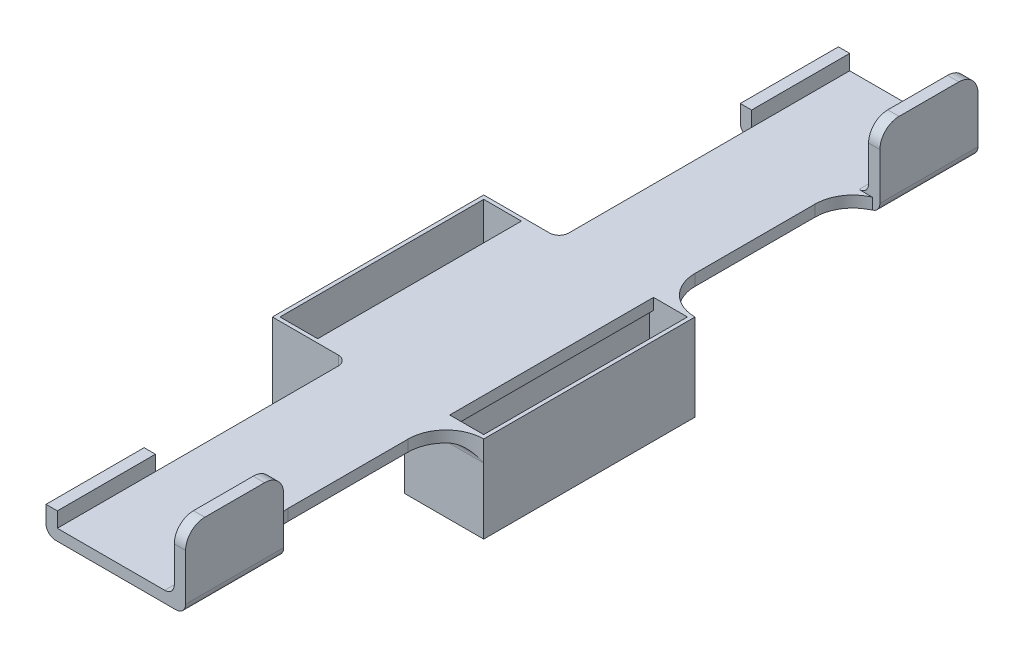
SolidWorks part; units mm, degrees
ref_plane "Front Plane" through (0, 0, 0) normal (0, 0, 1) x (1, 0, 0)
ref_plane "Top Plane" through (0, 0, 0) normal (0, 1, 0) x (1, 0, 0)
ref_plane "Right Plane" through (0, 0, 0) normal (1, 0, 0) x (0, 0, -1)
sketch "Sketch1" plane through (0, 0, 0) normal (0, 1, 0) x (1, 0, 0)
  line L1 (14, -14) -> (-14, -14)
  line L2 (14, -14) -> (14, 14)
  line L3 (14, 14) -> (-14, 14)
  line L4 (-14, -14) -> (-14, 14)
  line L5 (14, -14) -> (-14, 14) construction
  line L6 (14, 14) -> (-14, -14) construction
  line L7 (13.5, 13.5) -> (-13.5, 13.5)
  line L8 (13.5, 13.5) -> (13.5, -13.5)
  line L9 (13.5, -13.5) -> (-13.5, -13.5)
  line L10 (-13.5, 13.5) -> (-13.5, -13.5)
  line L11 (13.5, 13.5) -> (-13.5, -13.5) construction
  line L12 (13.5, -13.5) -> (-13.5, 13.5) construction
  point P0 (0, 0)
  point P6 (0, 0)
  dimension "D1" = 28
  dimension "D2" = 28
  dimension "D3" = 27
  dimension "D4" = 27
extrude "Boss-Extrude1" add sketch "Sketch1" along normal blind 5
sketch "Sketch2" plane through (0, 5, 0) normal (0, 1, 0) x (1, 0, 0)
  line L0 (-13.5, 13.5) -> (-13.5, -13.5) construction
  line L1 (-13.5, 13.5) -> (-13.5, -13.5)
  line L2 (-13.5, -13.5) -> (13.5, -13.5) construction
  line L3 (13.5, -13.5) -> (13.5, 13.5) construction
  line L4 (13.5, 13.5) -> (-13.5, 13.5) construction
  line L5 (-13.5, -13.5) -> (13.5, -13.5)
  line L6 (13.5, -13.5) -> (13.5, 13.5)
  line L7 (13.5, 13.5) -> (-13.5, 13.5)
extrude "Boss-Extrude2" add sketch "Sketch2" against normal blind 1 separate body
sketch "Sketch4" plane through (0, 0, 0) normal (0, -1, 0) x (1, 0, 0)
  line L0 (-14, 14) -> (14, 14) construction
  line L1 (-3.5, 14) -> (3.5, 14)
  line L2 (-3.5, 14) -> (-3.5, 13.5)
  line L3 (-3.5, 13.5) -> (3.5, 13.5)
  line L4 (3.5, 14) -> (3.5, 13.5)
  line L5 (-13.5, 13.5) -> (13.5, 13.5) construction
  line L6 (0, 0) -> (13.5, 0) construction
  line L7 (13.5, 13.5) -> (13.5, -13.5) construction
  line L8 (-3.5, -13.5) -> (3.5, -13.5)
  line L9 (3.5, -14) -> (3.5, -13.5)
  line L10 (-3.5, -14) -> (3.5, -14)
  line L11 (-3.5, -14) -> (-3.5, -13.5)
  dimension "D1" = 3.5
  dimension "D2" = 3.5
extrude "Cut-Extrude1" cut sketch "Sketch4" against normal up to surface (4 mm away) up to face at (0, 4, 0)
sketch "Sketch5" plane through (0, 4, 0) normal (0, -1, 0) x (1, 0, 0)
  line L0 (13.5, -13.5) -> (-13.5, -13.5) construction
  line L1 (-13.5, 13.5) -> (-8.5, 13.5)
  line L2 (-13.5, 13.5) -> (-13.5, -13.5)
  line L3 (-13.5, -13.5) -> (-8.5, -13.5)
  line L4 (-8.5, 13.5) -> (-8.5, -13.5)
  line L5 (0, 0) -> (0, 13.5) construction
  line L6 (-3.5, 13.5) -> (3.5, 13.5) construction
  line L7 (13.5, -13.5) -> (8.5, -13.5)
  line L8 (8.5, 13.5) -> (8.5, -13.5)
  line L9 (13.5, 13.5) -> (8.5, 13.5)
  line L10 (13.5, 13.5) -> (13.5, -13.5)
  dimension "D1" = 5
extrude "Cut-Extrude2" cut sketch "Sketch5" against normal through all both and the other way through all
sketch "Sketch6" plane through (0, 4, 0) normal (0, -1, 0) x (1, 0, 0)
  line L0 (-8.5, -1.5) -> (0, -1.5) construction
  line L2 (-8.5, -10.5) -> (0, -10.5) construction
  line L3 (0, 13.5) -> (0, -13.5) construction
  line L4 (-3.5, 13.5) -> (3.5, 13.5) construction
  line L5 (3.5, -13.5) -> (-3.5, -13.5) construction
  line L6 (8.5, -13.5) -> (-8.5, -13.5) construction
  line L8 (0, 0) -> (-8.5, 0) construction
  line L9 (-8.5, 13.5) -> (-8.5, -13.5) construction
  line L24 (-1.5, 0) -> (-1.5, -13.5) construction
  line L25 (-7, -13.5) -> (-7, 0) construction
  line L26 (-7, -10.5) -> (-1.5, -1.5)
  line L27 (-1.5, -1.5) -> (-1.5, -10.5)
  line L28 (-1.5, -10.5) -> (-7, -10.5)
  line L29 (-1.5, 10.5) -> (-7, 10.5)
  line L30 (-7, 10.5) -> (-1.5, 1.5)
  line L31 (-1.5, 1.5) -> (-1.5, 10.5)
  line L32 (1.5, 1.5) -> (1.5, 10.5)
  line L33 (1.5, 10.5) -> (7, 10.5)
  line L34 (7, 10.5) -> (1.5, 1.5)
  line L35 (7, -10.5) -> (1.5, -1.5)
  line L36 (1.5, -10.5) -> (7, -10.5)
  line L37 (1.5, -1.5) -> (1.5, -10.5)
  line L38 (-7, -9) -> (-1.5, 0)
  line L39 (-7, 9) -> (-1.5, 0)
  line L40 (7, 9) -> (1.5, 0)
  line L41 (7, -9) -> (1.5, 0)
  line L42 (-7, 9) -> (-7, -9)
  line L43 (7, 9) -> (7, -9)
  point P15 (-1.5, -10.5)
  point P19 (-7, -10.5)
  point P21 (-1.5, -1.5)
  point P23 (-7, -1.5)
  point P37 (-7, -9)
  dimension "D1" = 1.5
  dimension "D2" = 3
  dimension "D3" = 1.5
  dimension "D4" = 1.5
  dimension "D5" = 1.5
sketch "Sketch7" plane through (0, 4, 0) normal (0, -1, 0) x (1, 0, 0)
  line L0 (8.5, -13.5) -> (-8.5, -13.5) construction
  line L1 (-8.5, 13.5) -> (-3.5, 13.5)
  line L2 (-8.5, 13.5) -> (-8.5, -13.5)
  line L3 (-8.5, -13.5) -> (-3.5, -13.5)
  line L4 (-3.5, 13.5) -> (-3.5, -13.5)
  line L5 (-3.5, -13.5) -> (-13.5, -13.5) construction
  line L6 (13.5, -13.5) -> (3.5, -13.5) construction
  line L7 (8.5, 13.5) -> (3.5, 13.5)
  line L8 (8.5, 13.5) -> (8.5, -13.5)
  line L9 (8.5, -13.5) -> (3.5, -13.5)
  line L10 (3.5, 13.5) -> (3.5, -13.5)
extrude "Boss-Extrude3" add sketch "Sketch7" against normal up to surface (1 mm away) and the other way up to surface (4 mm away) up to face at (0, 5, 0) other way up to face at (8.625, 0, 0)
sketch "Sketch8" plane through (0, 0, 0) normal (0, -1, 0) x (1, 0, 0)
  line L0 (-13.5, -13.5) -> (-13.5, 13.5) construction
  line L5 (-3.5, -14) -> (-14, -14) construction
  line L6 (-14, -14) -> (-14, 14) construction
  line L7 (-14, 14) -> (-3.5, 14) construction
  line L8 (-13.5, -13.5) -> (-13.5, 13.5)
  line L13 (-3.5, -14) -> (-14, -14)
  line L14 (-14, -14) -> (-14, 14)
  line L15 (-14, 14) -> (-3.5, 14)
  line L17 (-13.5, -13.5) -> (-3.5, -13.5)
  line L18 (-3.5, 14) -> (-3.5, -14) construction
  line L23 (-3.5, 14) -> (-3.5, -14) construction
  line L29 (-3.5, 14) -> (-3.5, 13.5)
  line L30 (-3.5, -13.5) -> (-3.5, -14)
  line L31 (-13.5, 13.5) -> (-3.5, 13.5)
  line L32 (-3.5, 14) -> (-3.5, -14) construction
  line L35 (0, 14) -> (0, 0) construction
  line L36 (3.5, 14) -> (-3.5, 14) construction
  line L37 (3.5, -13.5) -> (3.5, -14)
  line L38 (13.5, -13.5) -> (3.5, -13.5)
  line L39 (3.5, -14) -> (14, -14)
  line L40 (14, -14) -> (14, 14)
  line L41 (13.5, -13.5) -> (13.5, 13.5)
  line L42 (3.5, 14) -> (3.5, 13.5)
  line L43 (14, 14) -> (3.5, 14)
  line L44 (13.5, 13.5) -> (3.5, 13.5)
extrude "Boss-Extrude4" add sketch "Sketch8" along normal blind 5 contours L17 L30 L13 L14 L15 L29 L31 L8
sketch "Sketch9" plane through (0, 0, 0) normal (0, -1, 0) x (1, 0, 0)
  line L6 (3.5, 14) -> (14, 14)
  line L10 (14, 14) -> (14, -14)
  line L11 (14, -14) -> (3.5, -14)
  line L12 (3.5, -14) -> (3.5, -13.5)
  line L13 (13.5, 13.5) -> (3.5, 13.5)
  line L14 (13.5, -13.5) -> (3.5, -13.5)
  line L15 (13.5, -13.5) -> (13.5, 13.5)
  line L16 (3.5, 13.5) -> (3.5, 14)
extrude "Boss-Extrude5" add sketch "Sketch9" along normal blind 5
sketch "Sketch10" plane through (0, 5, 0) normal (0, 1, 0) x (1, 0, 0)
  line L0 (9, 14.6081) -> (9, -15.0682) construction
  line L1 (14, -14) -> (14, 14) construction
  line L2 (-4, 14.6081) -> (-4, -15.0682) construction
  line L3 (0, 0) -> (9, 0) construction
  line L4 (-4, 52.5) -> (9, 52.5)
  line L5 (-4, 52.5) -> (-4, -52.5)
  line L6 (-4, -52.5) -> (9, -52.5)
  line L7 (9, 52.5) -> (9, -52.5)
  dimension "D1" = 5
  dimension "D2" = 13
  dimension "D3" = 52.5
  dimension "D4" = 52.5
extrude "Boss-Extrude6" add sketch "Sketch10" along normal blind 1.5
sketch "Sketch11" plane through (0, 5, 0) normal (0, 1, 0) x (1, 0, 0)
  line L0 (-13.5, -13.5) -> (-8.5, -13.5) construction
  line L1 (-8.5, 13.5) -> (-13.5, 13.5) construction
  line L2 (-13.5, 13.5) -> (-13.5, -13.5) construction
  line L3 (-13.5, -13.5) -> (-8.5, -13.5)
  line L4 (-14, -14) -> (-4, -14)
  line L5 (-4, -14) -> (-4, 14)
  line L6 (-4, 14) -> (-14, 14)
  line L7 (-14, 14) -> (-14, -14)
  line L8 (-14, -14) -> (-4, -14)
  line L9 (-4, -14) -> (-4, 14)
  line L10 (-4, 14) -> (-14, 14)
  line L11 (-14, 14) -> (-14, -14)
  line L12 (-8.5, 13.5) -> (-13.5, 13.5)
  line L13 (-13.5, 13.5) -> (-13.5, -13.5)
  line L14 (-8.5, -13.5) -> (-8.5, 13.5) construction
  line L15 (-8.5, -13.5) -> (-8.5, 13.5)
  line L16 (9, 13.5) -> (9, 14) construction
  line L17 (9, -14) -> (9, -13.5) construction
  line L18 (9, -13.5) -> (13.5, -13.5) construction
  line L19 (9, -14) -> (14, -14) construction
  line L20 (14, -14) -> (14, 14) construction
  line L21 (13.5, -13.5) -> (13.5, 13.5) construction
  line L22 (13.5, 13.5) -> (9, 13.5) construction
  line L23 (14, 14) -> (9, 14) construction
  line L24 (9, 13.5) -> (9, 14)
  line L25 (9, -14) -> (9, -13.5)
  line L26 (9, -13.5) -> (13.5, -13.5)
  line L27 (9, -14) -> (14, -14)
  line L28 (14, -14) -> (14, 14)
  line L29 (13.5, -13.5) -> (13.5, 13.5)
  line L30 (13.5, 13.5) -> (9, 13.5)
  line L31 (14, 14) -> (9, 14)
  dimension "D1" = 0
extrude "Boss-Extrude7" add sketch "Sketch11" along normal up to surface (1.5 mm away) up to face at (2.5, 6.5, 0)
sketch "Sketch12" plane through (0, 6.5, 0) normal (0, 1, 0) x (1, 0, 0)
  line L0 (9, -52.5) -> (9, -14) construction
  line L1 (9, -39.5) -> (12, -39.5)
  line L2 (9, -39.5) -> (9, -52.5)
  line L3 (9, -52.5) -> (12, -52.5)
  line L4 (12, -39.5) -> (12, -52.5)
  line L5 (0, 0) -> (22.7174, 0) construction
  line L6 (9, 39.5) -> (12, 39.5)
  line L7 (9, 39.5) -> (9, 52.5)
  line L8 (9, 52.5) -> (12, 52.5)
  line L9 (12, 39.5) -> (12, 52.5)
  dimension "D1" = 3
  dimension "D2" = 13
extrude "Boss-Extrude8" add sketch "Sketch12" against normal up to surface (1.5 mm away) contours L4 L3 L2 L1 up to face at (2.5, 5, -33.25)
sketch "Sketch14" plane through (0, 6.5, 0) normal (0, 1, 0) x (1, 0, 0)
  line L0 (12, -39.5) -> (12, -52.5) construction
  line L1 (9, 52.5) -> (12, 52.5)
  line L2 (9, 52.5) -> (9, 39.5)
  line L3 (9, 39.5) -> (12, 39.5)
  line L4 (12, 52.5) -> (12, 39.5)
  dimension "D1" = 13
extrude "Boss-Extrude9" add sketch "Sketch14" against normal up to surface (1.5 mm away) up to face at (2.5, 5, -33.25)
fillet "Fillet1" radius 5 4 edges at (9, 5.75, 39.5) (9, 5.75, 14) (9, 5.75, -14) (9, 5.75, -39.5)
sketch "Sketch15" plane through (12, 0, 0) normal (1, 0, 0) x (0, 0, -1)
  line L0 (-52.5, 5) -> (-52.5, 6.5) construction
  line L1 (52.5, 5) -> (39.5, 5)
  line L2 (52.5, 5) -> (52.5, 15)
  line L3 (52.5, 15) -> (39.5, 15)
  line L4 (39.5, 5) -> (39.5, 15)
  line L5 (-39.5, 5) -> (-52.5, 5)
  line L6 (-39.5, 5) -> (-39.5, 15)
  line L7 (-39.5, 15) -> (-52.5, 15)
  line L8 (-52.5, 5) -> (-52.5, 15)
  line L9 (39.5, 5) -> (39.5, 6.5) construction
  dimension "D1" = 10
extrude "Boss-Extrude10" add sketch "Sketch15" along normal blind 1 and the other way blind 0.5
fillet "Fillet2" radius 1.27 2 edges at (11.5, 6.5, 46) (11.5, 6.5, -46)
fillet "Fillet3" radius 1.27 2 edges at (5, 5, -14) (5, 5, 14)
fillet "Fillet4" radius 1.27 4 edges at (-8.5, 0, 0) (8.5, 0, 0) (3.5, 0, 0) (-3.5, 0, 0)
fillet "Fillet5" radius 1.27 2 edges at (-4, 5.115, -14) (-4, 5.115, 14)
sketch "Sketch16" plane through (-4, 0, 0) normal (-1, 0, 0) x (0, 0, 1)
  line L0 (-52.5, 8.5) -> (-39.5, 8.5)
  line L1 (52.5, 5) -> (39.5, 5)
  line L2 (52.5, 5) -> (52.5, 8.5)
  line L4 (39.5, 5) -> (39.5, 8.5)
  line L5 (-52.5, 5) -> (-39.5, 5)
  line L6 (-52.5, 5) -> (-52.5, 8.5)
  line L8 (-39.5, 5) -> (-39.5, 8.5)
  line L9 (-52.5, 6.5) -> (-15.27, 6.5) construction
  line L10 (39.5, 8.5) -> (52.5, 8.5)
  line L11 (52.5, 6.5) -> (39.5, 6.5) construction
  dimension "D1" = 2
  dimension "D2" = 13
  dimension "D3" = 2
  dimension "D4" = 13
extrude "Boss-Extrude11" add sketch "Sketch16" along normal blind 1.5
fillet "Fillet6" radius 1.27 2 edges at (-5.5, 5, 46) (-5.5, 5, -46)
fillet "Fillet7" radius 1.27 2 edges at (13, 5, 46) (13, 5, -46)
fillet "Fillet8" radius 2.54 4 edges at (12.25, 15, -52.5) (12.25, 15, -39.5) (12.25, 15, 39.5) (12.25, 15, 52.5)
sketch "Sketch17" plane through (0, 4, 0) normal (0, -1, 0) x (1, 0, 0)
  line L0 (3.5, 14.029) -> (-3.5, 14.029) construction
  line L2 (-2, 14.029) -> (-2, -14.029)
  line L5 (-3.5, -14.029) -> (3.5, -14.029) construction
  line L10 (2, 14.029) -> (2, -14.029)
  line L12 (-2, 14.029) -> (-2, 17.1757)
  line L13 (-2, 17.1757) -> (2, 17.1757)
  line L14 (2, 14.029) -> (2, 17.1757)
  line L16 (-2, -14.029) -> (-2, -17.474)
  line L17 (-2, -17.474) -> (2, -17.474)
  line L18 (2, -14.029) -> (2, -17.474)
  dimension "D1" = 4
  dimension "D2" = 2
extrude "Cut-Extrude3" cut sketch "Sketch17" against normal up to surface (1 mm away) up to face at (3.8493, 5, 34.2263)
